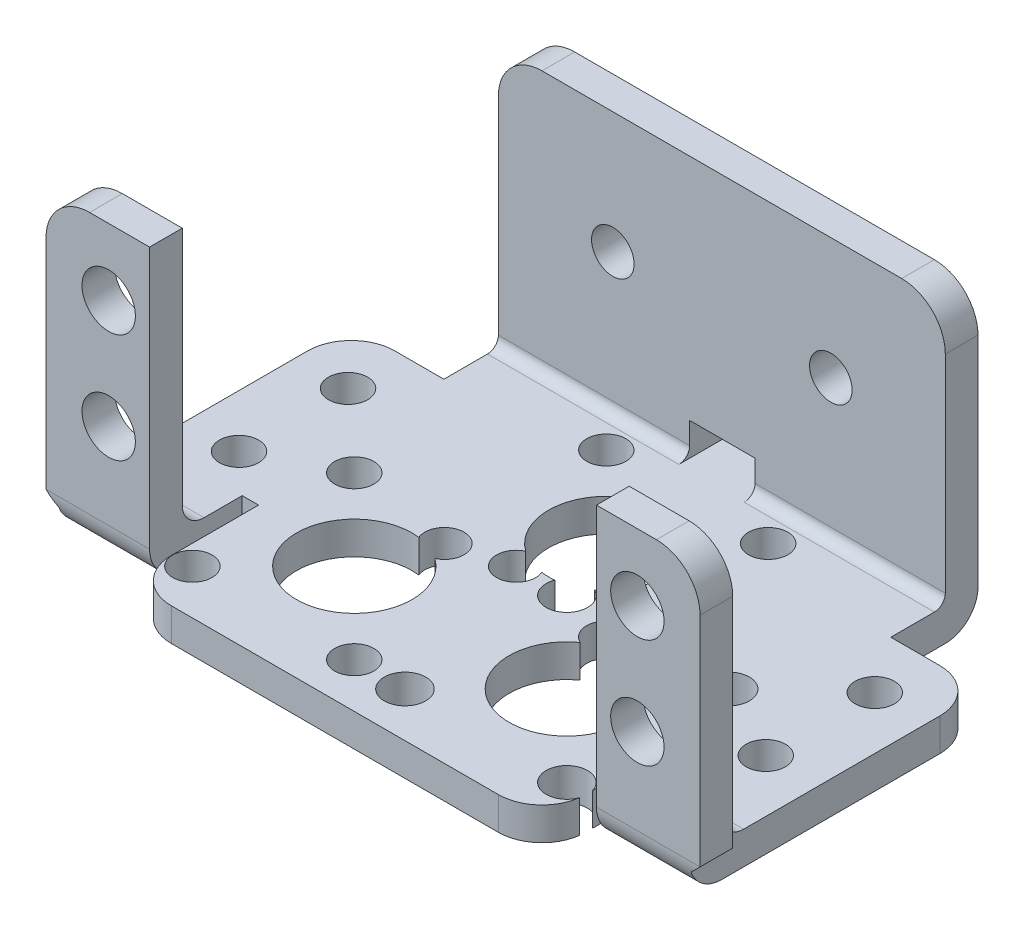
SolidWorks part; units mm, degrees
ref_plane "Alzado" through (0, 0, 0) normal (0, 0, 1) x (1, 0, 0)
ref_plane "Planta" through (0, 0, 0) normal (0, 1, 0) x (1, 0, 0)
ref_plane "Vista lateral" through (0, 0, 0) normal (1, 0, 0) x (0, 0, -1)
sketch "Croquis1" plane through (0, 0, 0) normal (0, 1, 0) x (1, 0, 0)
  line L0 (0, 11.75) -> (0, -11.75) construction
  line L1 (-20.5, 11.75) -> (20.5, 11.75)
  line L2 (-20.5, 11.75) -> (-20.5, -11.75)
  line L3 (-20.5, -11.75) -> (20.5, -11.75)
  line L4 (20.5, 11.75) -> (20.5, -11.75)
  line L5 (-20.5, 11.75) -> (20.5, -11.75) construction
  line L6 (-20.5, -11.75) -> (20.5, 11.75) construction
  line L7 (0, -55) -> (0, 55) construction
  circle A0 centre (0, 1.15) radius 5.3
  point P0 (0, 0)
  point P22 (0, 1.62)
  dimension "D6" = 10.6
  dimension "D1" = 23.5
  dimension "D2" = 41
  dimension "D3" = 10.6
extrude "Saliente-Extruir1" add sketch "Croquis1" along normal blind 3
sketch "Croquis3" plane through (0, 0, 0) normal (0, -1, 0) x (1, 0, 0)
  line L0 (20.5, -11.75) -> (-20.5, -11.75) construction
  line L1 (20.5, -11.75) -> (-20.5, -11.75)
  line L2 (20.5, -11.75) -> (20.5, -14.75)
  line L3 (20.5, -14.75) -> (-20.5, -14.75)
  line L4 (-20.5, -11.75) -> (-20.5, -14.75)
  line L5 (0, -11.75) -> (0, 142.4662) construction
  dimension "D1" = 3
  dimension "D2" = 41
extrude "Saliente-Extruir2" add sketch "Croquis3" against normal blind 27
sketch "Croquis4" plane through (0, 0, 0) normal (0, -1, 0) x (1, 0, 0)
  line L0 (-20.5, -14.75) -> (-20.5, 11.75) construction
  line L1 (-20.5, -6.75) -> (-25, -6.75)
  line L2 (-20.5, -6.75) -> (-20.5, 17.25)
  line L3 (-20.5, 17.25) -> (-29, 17.25)
  line L4 (-29, -2.75) -> (-29, 17.25)
  line L5 (-20.5, -11.75) -> (-20.5, 11.75) construction
  line L7 (20.5, -11.75) -> (-20.5, -11.75) construction
  line L8 (-24.1608, 13.0113) -> (-24.1608, -6.75) construction
  arc A0 (-29, -2.75) -> (-25, -6.75) centre (-25, -2.75) ccw
  circle A1 centre (-24.1608, -1.62) radius 1.8
  circle A2 centre (-24.1608, 8.38) radius 1.8
  dimension "D4" = 4
  dimension "D5" = 3.6
  dimension "D6" = 10
  dimension "D1" = 24
  dimension "D2" = 8.5
  dimension "D3" = 5
  dimension "D7" = 5.13
extrude "Saliente-Extruir3" add sketch "Croquis4" against normal blind 3
sketch "Croquis5" plane through (0, 0, 0) normal (0, -1, 0) x (1, 0, 0)
  line L1 (-29, 17.25) -> (-20.5, 17.25)
  line L2 (-29, 17.25) -> (-29, 20.25)
  line L3 (-29, 20.25) -> (-20.5, 20.25)
  line L4 (-20.5, 17.25) -> (-20.5, 20.25)
  dimension "D1" = 3
extrude "Saliente-Extruir4" add sketch "Croquis5" against normal blind 27
sketch "Croquis6" plane through (0, 0, 11.75) normal (0, 0, 1) x (1, 0, 0)
  line L0 (-20.5, 3) -> (20.5, 3) construction
  line L1 (-19, 3) -> (19, 3)
  line L2 (-19, 3) -> (-19, 0)
  line L3 (-19, 0) -> (19, 0)
  line L4 (19, 3) -> (19, 0)
  line L5 (-20.5, 0) -> (20.5, 0) construction
  line L6 (0, 3) -> (0, 0) construction
  dimension "D1" = 38
extrude "Saliente-Extruir5" add sketch "Croquis6" along normal blind 12
sketch "Croquis10" plane through (0, 0, 20.25) normal (0, 0, 1) x (1, 0, 0)
  line L0 (-24.25, 27) -> (-24.25, 0) construction
  line L1 (-20.5, 27) -> (-20.5, 0) construction
  line L2 (-20.5, 27) -> (-29, 27) construction
  line L3 (-20.5, 0) -> (-29, 0) construction
  line L4 (19, 3) -> (-19, 3) construction
  circle A0 centre (-24.25, 10.87) radius 2.45
  circle A1 centre (-24.25, 20.87) radius 2.45
  dimension "D1" = 4.9
  dimension "D2" = 10
  dimension "D3" = 3.75
  dimension "D4" = 7.87
extrude "Cortar-Extruir3" cut sketch "Croquis10" against normal up to next
ref_plane "Plano1" through (0, 0, 0) normal (1, 0, 0) x (0, 0, -1)
mirror "Simetría3" about plane through (0, 0, 0) normal (1, 0, 0) of "Cortar-Extruir3", "Saliente-Extruir3", "Saliente-Extruir4"
sketch "Croquis16" plane through (29, 0, 0) normal (1, 0, 0) x (0, 0, -1)
  line L0 (-17.25, 3) -> (2.75, 3) construction
  line L1 (-17.25, 27) -> (-20.25, 27)
  line L2 (-17.25, 27) -> (-17.25, 3)
  line L3 (-17.25, 3) -> (-20.25, 3)
  line L4 (-20.25, 27) -> (-20.25, 3)
  line L5 (-20.25, 27) -> (-20.25, 0) construction
extrude "Saliente-Extruir6" add sketch "Croquis16" along normal blind 1
sketch "Croquis17" plane through (-29, 0, 0) normal (-1, 0, 0) x (0, 0, 1)
  line L0 (20.25, 27) -> (20.25, 0) construction
  line L1 (17.25, 27) -> (20.25, 27)
  line L2 (17.25, 27) -> (17.25, 3)
  line L3 (17.25, 3) -> (20.25, 3)
  line L4 (20.25, 27) -> (20.25, 3)
extrude "Saliente-Extruir7" add sketch "Croquis17" along normal blind 1
sketch "Croquis8" plane through (0, 3, 0) normal (0, 1, 0) x (1, 0, 0)
  line L0 (0, 1.15) -> (0, -12.22) construction
  line L1 (0, -12.22) -> (-9.75, -12.22) construction
  line L2 (0, -14.85) -> (0, 14.85) construction
  circle A0 centre (-9.75, -12.22) radius 5.3
  circle A3 centre (0, 1.15) radius 5.3 construction
  point P14 (-9.75, -12.22)
  dimension "D5" = 13.37
  dimension "D6" = 9.75
extrude "Cortar-Extruir1" cut sketch "Croquis8" against normal up to next
mirror "Simetría4" about plane through (0, 0, 0) normal (1, 0, 0) of "Cortar-Extruir1"
sketch "Croquis9" plane through (0, 0, -14.75) normal (0, 0, -1) x (-1, 0, 0)
  line L0 (-20.3753, 15.87) -> (20.7294, 15.87) construction
  line L1 (20.5, 27) -> (-20.5, 27) construction
  line L2 (0, 27) -> (0, 0) construction
  line L8 (20.5, 3) -> (29, 3) construction
  circle A0 centre (-10, 15.87) radius 1.95
  circle A1 centre (10, 15.87) radius 1.95
  dimension "D1" = 3.9
  dimension "D2" = 20
  dimension "D3" = 12.87
extrude "Cortar-Extruir2" cut sketch "Croquis9" against normal up to next
fillet "Redondeo1" radius 4 6 edges at (-19, 1.5, 23.75) (19, 1.5, 23.75) (20.5, 27, -13.25) (-20.5, 27, -13.25) (-30, 27, 18.75) (30, 27, 18.75)
fillet "Redondeo2" radius 3 3 edges at (0, 0, -14.75) (24.75, 0, 20.25) (-24.75, 0, 20.25)
fillet "Redondeo3" radius 1 1 edges
fillet "Redondeo4" radius 2 2 edges at (24.75, 3, 17.25)
sketch "Croquis11" plane through (0, 0, 0) normal (0, 1, 0) x (1, 0, 0)
  line L0 (0, 1.15) -> (7.4246, -6.2746) construction
  line L1 (0, 1.15) -> (10.5, 1.15) construction
  circle A0 centre (0, 1.15) radius 10.5 construction
  circle A1 centre (7.4246, -6.2746) radius 1.8
  circle A2 centre (-7.4246, -6.2746) radius 1.8
  circle A3 centre (-7.4246, 8.5746) radius 1.8
  circle A4 centre (7.4246, 8.5746) radius 1.8
  point P14 (0, 1.15)
  dimension "D1" = 21
  dimension "D2" = 3.6
  dimension "D4" = 45
  dimension "D3" = 4
extrude "Cortar-Extruir4" cut sketch "Croquis11" along normal blind 5
sketch "Croquis12" plane through (0, 0, 0) normal (0, -1, 0) x (1, 0, 0)
  line L0 (-9.75, 12.22) -> (-2.3254, 19.6446) construction
  line L1 (-9.75, 12.22) -> (0.75, 12.22) construction
  circle A0 centre (-9.75, 12.22) radius 10.5 construction
  circle A1 centre (-2.3254, 19.6446) radius 1.8
  circle A2 centre (-2.3254, 4.7954) radius 1.8
  circle A3 centre (-17.1746, 4.7954) radius 1.8
  circle A4 centre (-17.1746, 19.6446) radius 1.8
  arc A5 (-6.6683, 7.908) -> (-9.0884, 6.9615) centre (-9.75, 12.22) ccw construction
  point P15 (-9.75, 12.22)
  dimension "D1" = 21
  dimension "D2" = 3.6
  dimension "D4" = 45
  dimension "D3" = 4
extrude "Cortar-Extruir5" cut sketch "Croquis12" against normal blind 5
sketch "Croquis14" plane through (0, 0, 0) normal (0, -1, 0) x (1, 0, 0)
  line L0 (17.1746, 19.6446) -> (9.75, 12.22) construction
  line L1 (9.75, 12.22) -> (20.25, 12.22) construction
  circle A0 centre (9.75, 12.22) radius 10.5 construction
  circle A1 centre (17.1746, 19.6446) radius 1.9
  circle A2 centre (17.1746, 4.7954) radius 1.9
  circle A3 centre (2.3254, 4.7954) radius 1.9
  circle A4 centre (2.3254, 19.6446) radius 1.9
  point P14 (9.75, 12.22)
  dimension "D1" = 21
  dimension "D2" = 3.8
  dimension "D4" = 45
  dimension "D3" = 4
extrude "Cortar-Extruir6" cut sketch "Croquis14" against normal blind 5
sketch "Croquis15" plane through (0, 0, -14.75) normal (0, 0, -1) x (-1, 0, 0)
  line L1 (2.9501, 6) -> (-3.0499, 6)
  line L2 (2.9501, 6) -> (2.9501, 3)
  line L3 (2.9501, 3) -> (-3.0499, 3)
  line L4 (-3.0499, 6) -> (-3.0499, 3)
  line L6 (-20.5, 3) -> (20.5, 3) construction
  dimension "D1" = 6
  dimension "D2" = 3
extrude "Cortar-Extruir7" cut sketch "Croquis15" against normal blind 6
chamfer "Chaflán1" distance 1 angle 45 2 edges at (29, 3, 18.75)
